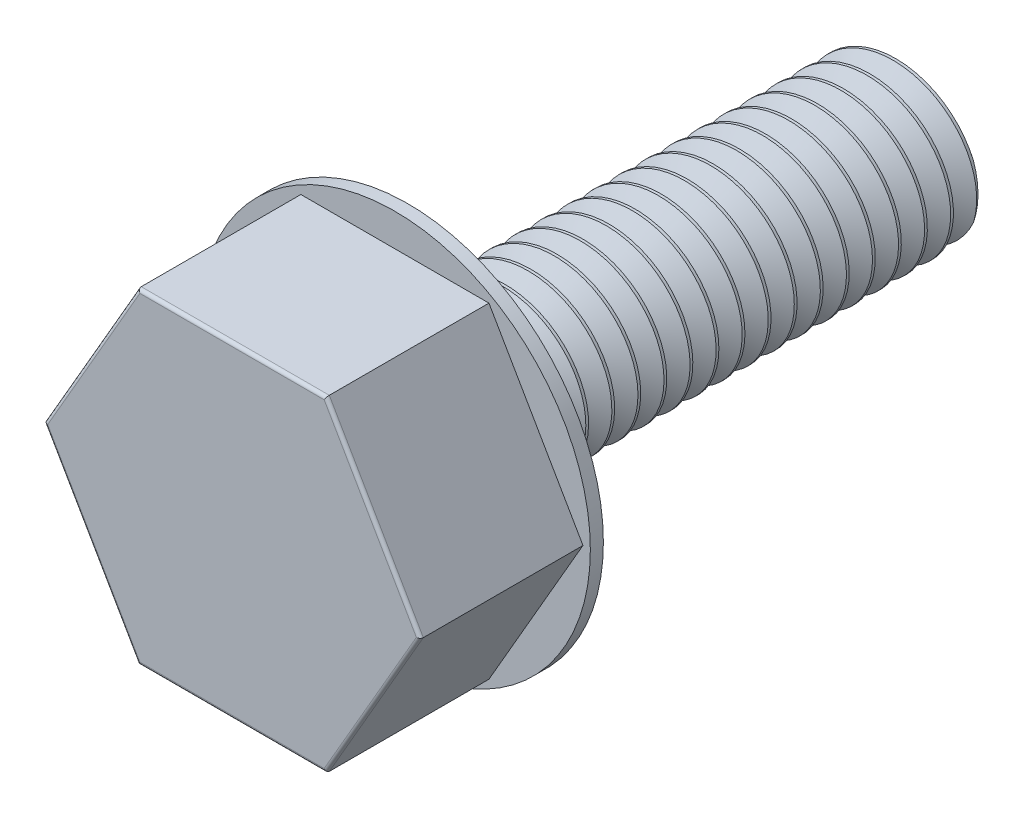
SolidWorks part; units mm, degrees
ref_plane "Front Plane" through (0, 0, 0) normal (1, 0, 0) x (0, 1, 0)
ref_plane "Top Plane" through (0, 0, 0) normal (0, 0, 1) x (0, 1, 0)
ref_plane "Right Plane" through (0, 0, 0) normal (0, 1, 0) x (-1, 0, 0)
sketch "Sketch3" plane through (0, 0, 0) normal (0, 0, 1) x (0, 1, 0)
  circle A0 centre (0, 0) radius 2.5
  dimension "D1" = 5
extrude "Boss-Extrude1" add sketch "Sketch3" along normal blind 15
sketch "Sketch4" plane through (0, 0, 0) normal (0, 0, -1) x (1, 0, 0)
  circle A0 centre (0, 0) radius 2.5
  dimension "D1" = 5
curve "Helix/Spiral1" pitch 0.8 height 15 turns 18.75
sketch "Sketch18" plane through (0, 0, 15) normal (0, 0, 1) x (1, 0, 0)
  circle A0 centre (0, 0) radius 6
  dimension "D1" = 12
extrude "Boss-Extrude2" add sketch "Sketch18" along normal blind 0.4
sketch "Sketch23" plane through (0, 0, 0) normal (0, 1, 0) x (-1, 0, 0)
  line L4 (1.8807, 0) -> (2.8097, -0.5363)
  line L5 (2.8097, -0.5363) -> (2.8097, 0.5363)
  line L6 (2.8097, 0.5363) -> (1.8807, 0)
  circle A0 centre (2.5, 0) radius 0.3097 construction
  spline S1 degree 3 poles (2.5, 0) (2.5, 0.0166) (2.3698, 0.05) (1.8138, 0.1) (0.9816, 0.15) (0, 0.2) (-0.9816, 0.25) (-1.8138, 0.3) (-2.3698, 0.35) (-2.5651, 0.4) (-2.3698, 0.45) (-1.8138, 0.5) (-0.7042, 0.5667) (0.7042, 0.6333) (1.8138, 0.7) (2.3698, 0.75) (2.5651, 0.8) (2.3698, 0.85) (1.8138, 0.9) (0.7042, 0.9667) (-0.7042, 1.0333) (-1.8138, 1.1) (-2.3698, 1.15) (-2.5651, 1.2) (-2.3698, 1.25) (-1.8138, 1.3) (-0.7042, 1.3667) (0.7042, 1.4333) (1.8138, 1.5) (2.3698, 1.55) (2.5651, 1.6) (2.3698, 1.65) (1.8138, 1.7) (0.7042, 1.7667) (-0.7042, 1.8333) (-1.8138, 1.9) (-2.3698, 1.95) (-2.5651, 2) (-2.3698, 2.05) (-1.8138, 2.1) (-0.7042, 2.1667) (0.7042, 2.2333) (1.8138, 2.3) (2.3698, 2.35) (2.5651, 2.4) (2.3698, 2.45) (1.8138, 2.5) (0.7042, 2.5667) (-0.7042, 2.6333) (-1.8138, 2.7) (-2.3698, 2.75) (-2.5651, 2.8) (-2.3698, 2.85) (-1.8138, 2.9) (-0.7042, 2.9667) (0.7042, 3.0333) (1.8138, 3.1) (2.3698, 3.15) (2.5651, 3.2) (2.3698, 3.25) (1.8138, 3.3) (0.7042, 3.3667) (-0.7042, 3.4333) (-1.8138, 3.5) (-2.3698, 3.55) (-2.5651, 3.6) (-2.3698, 3.65) (-1.8138, 3.7) (-0.7042, 3.7667) (0.7042, 3.8333) (1.8138, 3.9) (2.3698, 3.95) (2.5651, 4) (2.3698, 4.05) (1.8138, 4.1) (0.7042, 4.1667) (-0.7042, 4.2333) (-1.8138, 4.3) (-2.3698, 4.35) (-2.5651, 4.4) (-2.3698, 4.45) (-1.8138, 4.5) (-0.7042, 4.5667) (0.7042, 4.6333) (1.8138, 4.7) (2.3698, 4.75) (2.5651, 4.8) (2.3698, 4.85) (1.8138, 4.9) (0.7042, 4.9667) (-0.7042, 5.0333) (-1.8138, 5.1) (-2.3698, 5.15) (-2.5651, 5.2) (-2.3698, 5.25) (-1.8138, 5.3) (-0.7042, 5.3667) (0.7042, 5.4333) (1.8138, 5.5) (2.3698, 5.55) (2.5651, 5.6) (2.3698, 5.65) (1.8138, 5.7) (0.7042, 5.7667) (-0.7042, 5.8333) (-1.8138, 5.9) (-2.3698, 5.95) (-2.5651, 6) (-2.3698, 6.05) (-1.8138, 6.1) (-0.7042, 6.1667) (0.7042, 6.2333) (1.8138, 6.3) (2.3698, 6.35) (2.5651, 6.4) (2.3698, 6.45) (1.8138, 6.5) (0.7042, 6.5667) (-0.7042, 6.6333) (-1.8138, 6.7) (-2.3698, 6.75) (-2.5651, 6.8) (-2.3698, 6.85) (-1.8138, 6.9) (-0.7042, 6.9667) (0.7042, 7.0333) (1.8138, 7.1) (2.3698, 7.15) (2.5651, 7.2) (2.3698, 7.25) (1.8138, 7.3) (0.7042, 7.3667) (-0.7042, 7.4333) (-1.8138, 7.5) (-2.3698, 7.55) (-2.5651, 7.6) (-2.3698, 7.65) (-1.8138, 7.7) (-0.7042, 7.7667) (0.7042, 7.8333) (1.8138, 7.9) (2.3698, 7.95) (2.5651, 8) (2.3698, 8.05) (1.8138, 8.1) (0.7042, 8.1667) (-0.7042, 8.2333) (-1.8138, 8.3) (-2.3698, 8.35) (-2.5651, 8.4) (-2.3698, 8.45) (-1.8138, 8.5) (-0.7042, 8.5667) (0.7042, 8.6333) (1.8138, 8.7) (2.3698, 8.75) (2.5651, 8.8) (2.3698, 8.85) (1.8138, 8.9) (0.7042, 8.9667) (-0.7042, 9.0333) (-1.8138, 9.1) (-2.3698, 9.15) (-2.5651, 9.2) (-2.3698, 9.25) (-1.8138, 9.3) (-0.7042, 9.3667) (0.7042, 9.4333) (1.8138, 9.5) (2.3698, 9.55) (2.5651, 9.6) (2.3698, 9.65) (1.8138, 9.7) (0.7042, 9.7667) (-0.7042, 9.8333) (-1.8138, 9.9) (-2.3698, 9.95) (-2.5651, 10) (-2.3698, 10.05) (-1.8138, 10.1) (-0.7042, 10.1667) (0.7042, 10.2333) (1.8138, 10.3) (2.3698, 10.35) (2.5651, 10.4) (2.3698, 10.45) (1.8138, 10.5) (0.7042, 10.5667) (-0.7042, 10.6333) (-1.8138, 10.7) (-2.3698, 10.75) (-2.5651, 10.8) (-2.3698, 10.85) (-1.8138, 10.9) (-0.7042, 10.9667) (0.7042, 11.0333) (1.8138, 11.1) (2.3698, 11.15) (2.5651, 11.2) (2.3698, 11.25) (1.8138, 11.3) (0.7042, 11.3667) (-0.7042, 11.4333) (-1.8138, 11.5) (-2.3698, 11.55) (-2.5651, 11.6) (-2.3698, 11.65) (-1.8138, 11.7) (-0.7042, 11.7667) (0.7042, 11.8333) (1.8138, 11.9) (2.3698, 11.95) (2.5651, 12) (2.3698, 12.05) (1.8138, 12.1) (0.7042, 12.1667) (-0.7042, 12.2333) (-1.8138, 12.3) (-2.3698, 12.35) (-2.5651, 12.4) (-2.3698, 12.45) (-1.8138, 12.5) (-0.7042, 12.5667) (0.7042, 12.6333) (1.8138, 12.7) (2.3698, 12.75) (2.5651, 12.8) (2.3698, 12.85) (1.8138, 12.9) (0.7042, 12.9667) (-0.7042, 13.0333) (-1.8138, 13.1) (-2.3698, 13.15) (-2.5651, 13.2) (-2.3698, 13.25) (-1.8138, 13.3) (-0.7042, 13.3667) (0.7042, 13.4333) (1.8138, 13.5) (2.3698, 13.55) (2.5651, 13.6) (2.3698, 13.65) (1.8138, 13.7) (0.7042, 13.7667) (-0.7042, 13.8333) (-1.8138, 13.9) (-2.3698, 13.95) (-2.5651, 14) (-2.3698, 14.05) (-1.8138, 14.1) (-0.7042, 14.1667) (0.7042, 14.2333) (1.8138, 14.3) (2.3698, 14.35) (2.5651, 14.4) (2.3698, 14.45) (1.8138, 14.5) (0.7042, 14.5667) (-0.7042, 14.6333) (-1.8138, 14.7) (-2.3698, 14.75) (-2.5651, 14.8) (-2.3699, 14.85) (-1.8135, 14.9) (-0.9826, 14.95) (-0.3252, 14.9834) (0, 15) knots 0 0 0 0 0.003333 0.006667 0.01 0.013333 0.016667 0.02 0.023333 0.026667 0.03 0.033333 0.036667 0.043333 0.046667 0.05 0.053333 0.056667 0.06 0.063333 0.07 0.073333 0.076667 0.08 0.083333 0.086667 0.09 0.096667 0.1 0.103333 0.106667 0.11 0.113333 0.116667 0.123333 0.126667 0.13 0.133333 0.136667 0.14 0.143333 0.15 0.153333 0.156667 0.16 0.163333 0.166667 0.17 0.176667 0.18 0.183333 0.186667 0.19 0.193333 0.196667 0.203333 0.206667 0.21 0.213333 0.216667 0.22 0.223333 0.23 0.233333 0.236667 0.24 0.243333 0.246667 0.25 0.256667 0.26 0.263333 0.266667 0.27 0.273333 0.276667 0.283333 0.286667 0.29 0.293333 0.296667 0.3 0.303333 0.31 0.313333 0.316667 0.32 0.323333 0.326667 0.33 0.336667 0.34 0.343333 0.346667 0.35 0.353333 0.356667 0.363333 0.366667 0.37 0.373333 0.376667 0.38 0.383333 0.39 0.393333 0.396667 0.4 0.403333 0.406667 0.41 0.416667 0.42 0.423333 0.426667 0.43 0.433333 0.436667 0.443333 0.446667 0.45 0.453333 0.456667 0.46 0.463333 0.47 0.473333 0.476667 0.48 0.483333 0.486667 0.49 0.496667 0.5 0.503333 0.506667 0.51 0.513333 0.516667 0.523333 0.526667 0.53 0.533333 0.536667 0.54 0.543333 0.55 0.553333 0.556667 0.56 0.563333 0.566667 0.57 0.576667 0.58 0.583333 0.586667 0.59 0.593333 0.596667 0.603333 0.606667 0.61 0.613333 0.616667 0.62 0.623333 0.63 0.633333 0.636667 0.64 0.643333 0.646667 0.65 0.656667 0.66 0.663333 0.666667 0.67 0.673333 0.676667 0.683333 0.686667 0.69 0.693333 0.696667 0.7 0.703333 0.71 0.713333 0.716667 0.72 0.723333 0.726667 0.73 0.736667 0.74 0.743333 0.746667 0.75 0.753333 0.756667 0.763333 0.766667 0.77 0.773333 0.776667 0.78 0.783333 0.79 0.793333 0.796667 0.8 0.803333 0.806667 0.81 0.816667 0.82 0.823333 0.826667 0.83 0.833333 0.836667 0.843333 0.846667 0.85 0.853333 0.856667 0.86 0.863333 0.87 0.873333 0.876667 0.88 0.883333 0.886667 0.89 0.896667 0.9 0.903333 0.906667 0.91 0.913333 0.916667 0.923333 0.926667 0.93 0.933333 0.936667 0.94 0.943333 0.95 0.953333 0.956667 0.96 0.963333 0.966667 0.97 0.976667 0.98 0.983333 0.986667 0.99 0.993333 0.996667 1 1 1 1 construction
sweep "Cut-Sweep3" cut profiles "Sketch23" path "Helix/Spiral1" align with end faces yes
sketch "Sketch24" plane through (0, 0, 15.4) normal (0, 0, 1) x (1, 0, 0)
  line L1 (5.7735, 0) -> (2.8868, 5)
  line L2 (2.8868, 5) -> (-2.8868, 5)
  line L3 (-2.8868, 5) -> (-5.7735, 0)
  line L4 (-5.7735, 0) -> (-2.8868, -5)
  line L5 (-2.8868, -5) -> (2.8868, -5)
  line L6 (2.8868, -5) -> (5.7735, 0)
  circle A0 centre (0, 0) radius 5 construction
  dimension "D1" = 10
extrude "Boss-Extrude3" add sketch "Sketch24" along normal blind 5
fillet "Fillet2" radius 0.1 6 edges at (0, -5, 20.4) (-4.3301, -2.5, 20.4) (-4.3301, 2.5, 20.4) (0, 5, 20.4) (4.3301, 2.5, 20.4) (4.3301, -2.5, 20.4)
